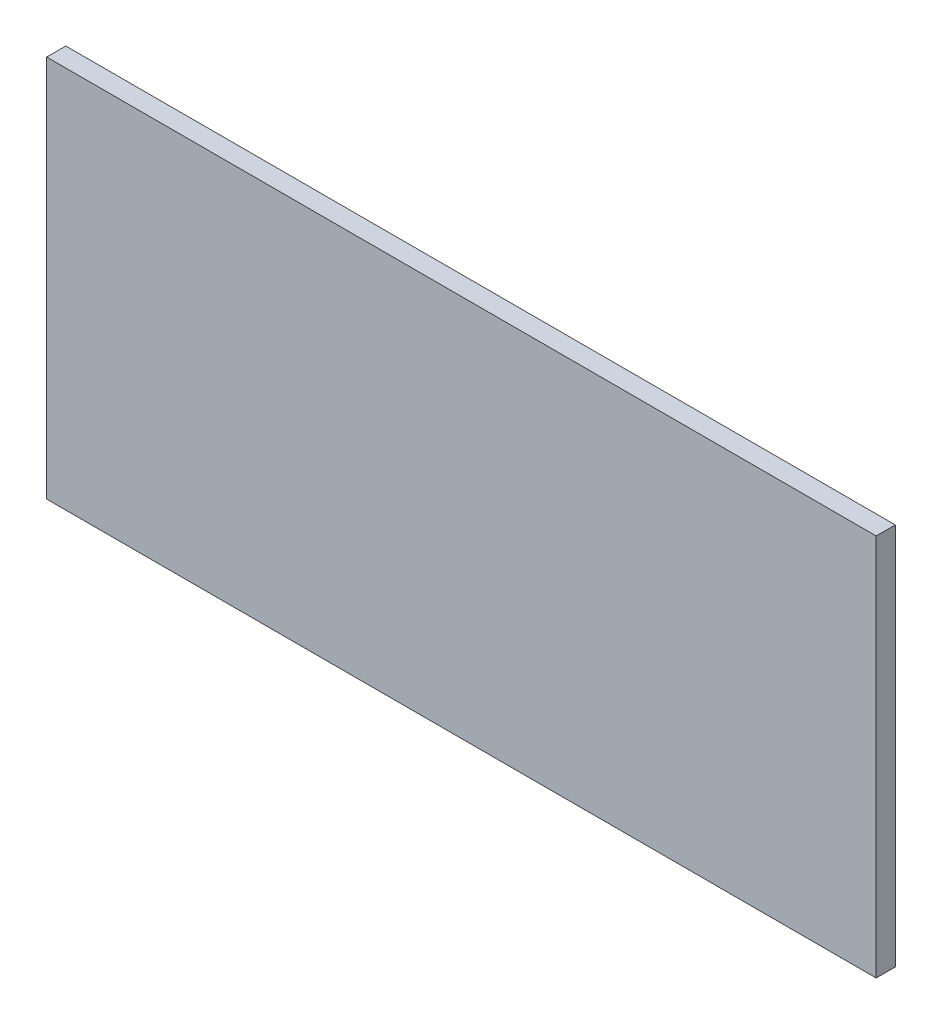
SolidWorks part; units mm, degrees
ref_plane "Front Plane" through (0, 0, 0) normal (0, 0, 1) x (1, 0, 0)
ref_plane "Top Plane" through (0, 0, 0) normal (0, 1, 0) x (1, 0, 0)
ref_plane "Right Plane" through (0, 0, 0) normal (1, 0, 0) x (0, 0, -1)
sketch "Sketch1" plane through (0, 0, 0) normal (0, 0, 1) x (1, 0, 0)
  line L0 (159.7602, 27.8614) -> (159.7602, 8.8614) construction
  line L1 (134.7602, 27.8614) -> (184.7602, 27.8614) construction
  line L2 (184.7602, 8.8614) -> (134.7602, 8.8614) construction
  line L3 (127.2602, 33.3614) -> (127.2602, 3.3614) construction
  line L5 (192.2602, 3.3614) -> (192.2602, 33.3614) construction
  line L6 (192.2602, 33.3614) -> (127.2602, 33.3614) construction
  line L7 (127.2602, 33.3614) -> (127.2602, 3.3614) construction
  line L8 (192.2602, 3.3614) -> (127.2602, 33.3614) construction
  line L9 (192.2602, 33.3614) -> (127.2602, 3.3614) construction
  line L12 (192.2602, 33.3614) -> (127.2602, 33.3614) construction
  line L13 (127.2602, 3.3614) -> (127.2602, 33.3614)
  line L14 (127.2602, 33.3614) -> (192.2602, 33.3614)
  line L15 (192.2602, 33.3614) -> (192.2602, 3.3614)
  line L16 (192.2602, 3.3614) -> (127.2602, 3.3614)
  point P6 (159.7602, 18.3614)
  dimension "D1" = 65
  dimension "D2" = 30
extrude "Boss-Extrude1" add sketch "Sketch1" against normal blind 1.5
sketch "Sketch2" plane through (0, 0, -1.5) normal (0, 0, -1) x (-1, 0, 0)
  line L0 (-184.7602, 25.3614) -> (-134.7602, 25.3614) construction
  line L1 (-184.7602, 8.8614) -> (-184.7602, 27.8614) construction
  line L2 (-134.7602, 8.8614) -> (-134.7602, 27.8614) construction
  line L3 (-184.7602, 11.3614) -> (-134.7602, 11.3614) construction
  line L4 (-137.2602, 27.8614) -> (-137.2602, 8.8614) construction
  line L5 (-134.7602, 27.8614) -> (-184.7602, 27.8614) construction
  line L6 (-184.7602, 8.8614) -> (-134.7602, 8.8614) construction
  line L7 (-182.2602, 27.8614) -> (-182.2602, 8.8614) construction
  line L8 (-182.2602, 27.8614) -> (-137.2602, 27.8614)
  line L9 (-134.7602, 25.3614) -> (-134.7602, 11.3614)
  line L10 (-137.2602, 8.8614) -> (-182.2602, 8.8614)
  line L12 (-184.7602, 11.3614) -> (-184.7602, 25.3614)
  arc A0 (-184.7602, 25.3614) -> (-182.2602, 27.8614) centre (-182.2602, 25.3614) cw
  arc A1 (-137.2602, 27.8614) -> (-134.7602, 25.3614) centre (-137.2602, 25.3614) cw
  arc A2 (-137.2602, 8.8614) -> (-134.7602, 11.3614) centre (-137.2602, 11.3614) ccw
  arc A3 (-182.2602, 8.8614) -> (-184.7602, 11.3614) centre (-182.2602, 11.3614) cw
  dimension "D1" = 2.5
extrude "Boss-Extrude2" add sketch "Sketch2" along normal blind 1.5 separate body
